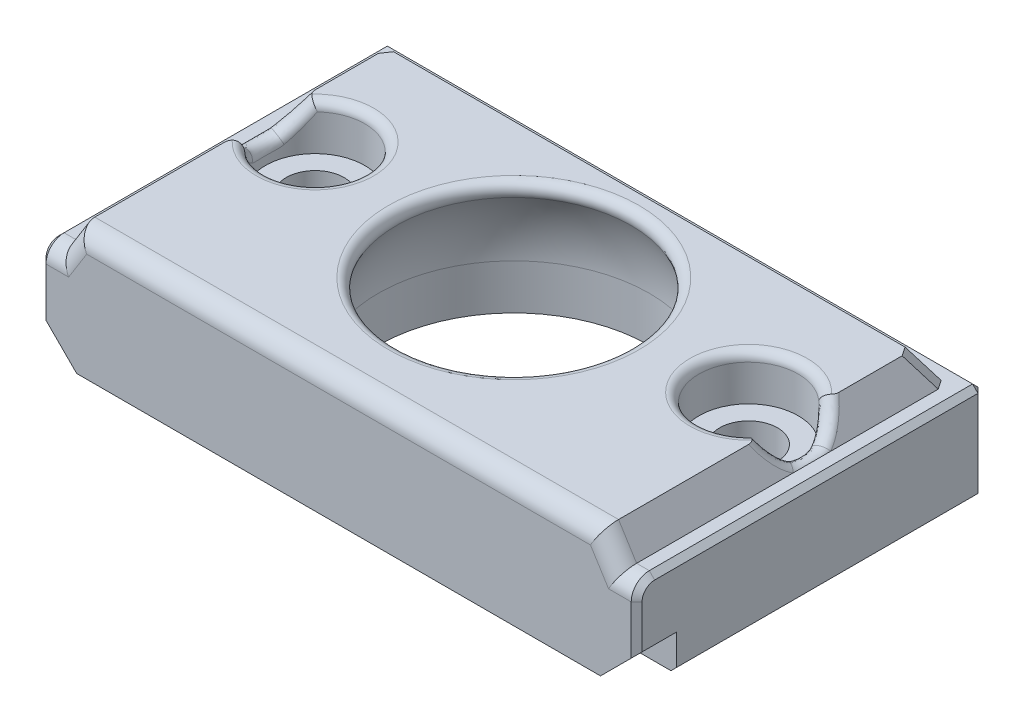
SolidWorks part; units mm, degrees
ref_plane "前视基准面" through (0, 0, 0) normal (0, 0, 1) x (1, 0, 0)
ref_plane "上视基准面" through (0, 0, 0) normal (0, 1, 0) x (1, 0, 0)
ref_plane "右视基准面" through (0, 0, 0) normal (1, 0, 0) x (0, 0, -1)
other "Configuration Table"
sketch "草图1" plane through (0, 0, 0) normal (0, 1, 0) x (1, 0, 0)
  line L0 (24.1165, 0) -> (24.1165, 19.2)
  line L1 (24.1165, 19.2) -> (57.1165, 19.2)
  line L2 (57.1165, 19.2) -> (57.1165, 0)
  line L3 (57.1165, 0) -> (24.1165, 0)
extrude "凸台-拉伸1" add sketch "草图1" along normal blind 7
ref_plane "基准面1" through (40.6165, 0, 0) normal (-1, 0, 0) x (0, 0, 1)
sketch "草图2" plane through (40.6165, 0, 0) normal (-1, 0, 0) x (0, 0, 1)
  line L1 (-19.2, 0) -> (0, 0) construction
  line L2 (-2.2, 2.5) -> (-2.2, 0)
  line L3 (-2.2, 0) -> (-9.7, 0)
  line L4 (-9.7, 0) -> (-9.7, 7)
  line L5 (-19.2, 7) -> (0, 7) construction
  line L6 (-9.7, 7) -> (-3.7, 7)
  arc A0 (-2.2, 2.5) -> (-3.7, 7) centre (-9.7, 2.5) ccw
revolve "切除-旋转1" cut sketch "草图2" angle 360 about L4
sketch "草图3" plane through (0, 0, 0) normal (0, 0, 1) x (1, 0, 0)
  line L0 (24.1165, 7) -> (24.1165, 5.4)
  line L1 (24.1165, 7) -> (24.1165, 0) construction
  line L2 (24.1165, 5.4) -> (25.1165, 5.4)
  line L3 (24.1165, 7) -> (26.1165, 7)
  line L4 (24.1165, 7) -> (57.1165, 7) construction
  line L5 (26.1165, 7) -> (25.1165, 5.4)
  line L8 (55.1165, 7) -> (56.1165, 5.4)
  line L9 (57.1165, 7) -> (55.1165, 7)
  line L10 (57.1165, 5.4) -> (56.1165, 5.4)
  line L11 (57.1165, 7) -> (57.1165, 5.4)
extrude "切除-拉伸1" cut sketch "草图3" against normal through all
sketch "草图4" plane through (24.1165, 0, 0) normal (-1, 0, 0) x (0, 0, 1)
  line L0 (-19.2, 5.4) -> (-19.2, 7)
  line L1 (-19.2, 7) -> (-17.2, 7)
  line L2 (-19.2, 7) -> (0, 7) construction
  line L3 (-17.2, 7) -> (-18.2, 5.4)
  line L4 (-19.2, 5.4) -> (0, 5.4) construction
  line L5 (-18.2, 5.4) -> (-19.2, 5.4)
extrude "切除-拉伸2" cut sketch "草图4" against normal through all
sketch "草图5" plane through (0, 7, 0) normal (0, 1, 0) x (1, 0, 0)
  circle A0 centre (28.6165, 10.7) radius 1.6
  circle A1 centre (52.6165, 10.7) radius 1.6
extrude "切除-拉伸3" cut sketch "草图5" against normal through all
sketch "草图6" plane through (0, 7, 0) normal (0, 1, 0) x (1, 0, 0)
  circle A0 centre (28.6165, 10.7) radius 2.75
  circle A1 centre (52.6165, 10.7) radius 2.75
extrude "切除-拉伸4" cut sketch "草图6" against normal blind 2.5
sketch "草图7" plane through (0, 0, 0) normal (0, 0, 1) x (1, 0, 0)
  line L0 (24.1165, 0) -> (26.1165, 0)
  line L1 (24.1165, 0) -> (57.1165, 0) construction
  line L2 (24.1165, 0) -> (24.1165, 2)
  line L3 (24.1165, 5.4) -> (24.1165, 0) construction
  line L4 (24.1165, 2) -> (26.1165, 0)
  line L5 (57.1165, 0) -> (57.1165, 2)
  line L6 (57.1165, 5.4) -> (57.1165, 0) construction
  line L7 (57.1165, 2) -> (55.1165, 0)
  line L8 (55.1165, 0) -> (57.1165, 0)
extrude "切除-拉伸5" cut sketch "草图7" against normal blind 2.2
fillet "圆角1" radius 1 5 edges at (56.6165, 5.4, 0) (55.6165, 6.2, 0) (40.6165, 7, 0) (25.6165, 6.2, 0) (24.6165, 5.4, 0)
fillet "圆角2" radius 0.5 5 edges at (55.3665, 6.6, -10.7) (25.8665, 6.6, -10.7) (49.8665, 7, -10.7) (31.3665, 7, -10.7) (40.6165, 7, -15.7)
chamfer "倒角1" distance 0.3 angle 45 14 edges at (57.1165, 3.2, 0) (24.1165, 3.2, 0) (57.1165, 5.1071, -0.2929) (24.1165, 5.1071, -0.2929) (24.1165, 0, -10.7) (57.1165, 0, -10.7) (40.6165, 0, -19.2) (57.1165, 2.7, -19.2) (57.1165, 5.4, -10.1) (24.1165, 5.4, -10.1) (40.6165, 5.4, -19.2) (24.1165, 2.7, -19.2) (55.6165, 6.2, -17.7) (25.6165, 6.2, -17.7) first distance on face at (40.6165, 3.36, 0) first distance on face at (56.5067, 5.0036, -0.3964) first distance on face at (24.7264, 5.0036, -0.3964) first distance on face at (40.6165, 0, -5.9) first distance on face at (40.6165, 2.7, -19.2) first distance on face at (40.6165, 5.4, -10.1333) first distance on face at (40.6165, 6.2, -17.7)
